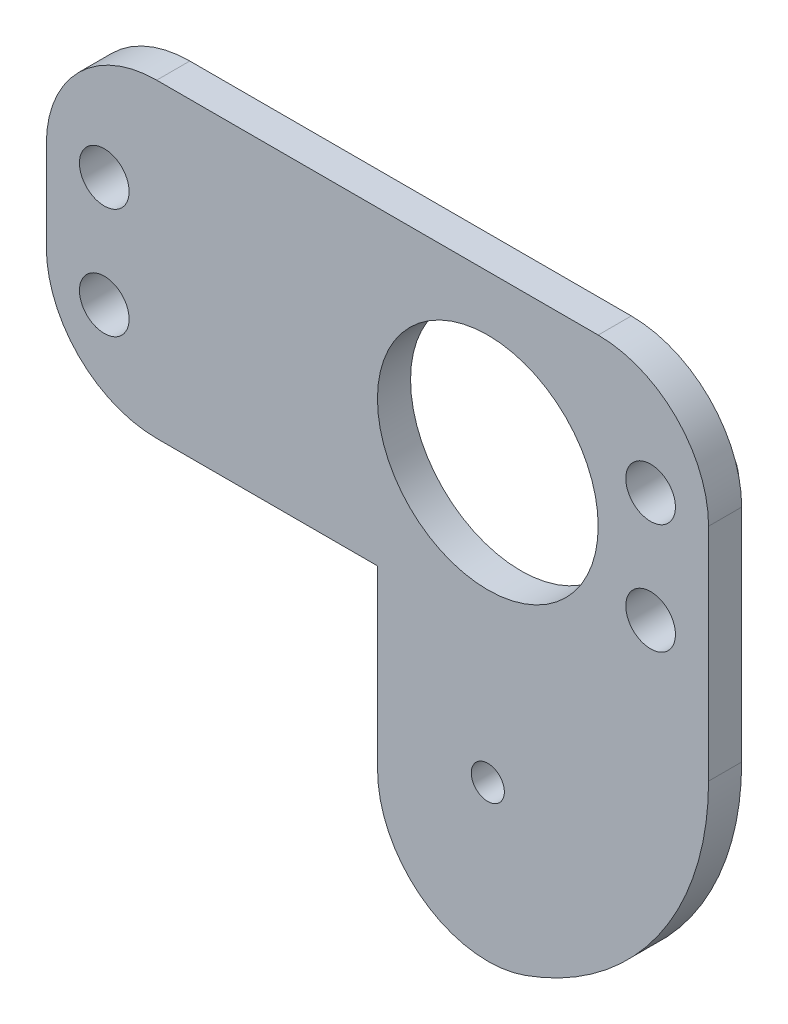
SolidWorks part; units mm, degrees
ref_plane "前视基准面" through (0, 0, 0) normal (0, 0, 1) x (1, 0, 0)
ref_plane "上视基准面" through (0, 0, 0) normal (0, 1, 0) x (1, 0, 0)
ref_plane "右视基准面" through (0, 0, 0) normal (1, 0, 0) x (0, 0, -1)
sketch "草图3" plane through (0, 0, 0) normal (0, 0, 1) x (1, 0, 0)
  line L0 (60.2665, 6.5325) -> (60.2665, 16.5325)
  line L1 (10.7665, 16.5325) -> (10.7665, 6.5325)
  line L2 (10.7665, 16.5325) -> (60.2665, 16.5325)
  circle A0 centre (60.2665, 16.5325) radius 3
  circle A1 centre (60.2665, 6.5325) radius 3
  circle A6 centre (10.7665, 6.5325) radius 3
  circle A7 centre (10.7665, 16.5325) radius 3
  dimension "D1" = 6
  dimension "D2" = 6
  dimension "D4" = 6
  dimension "D5" = 6
  dimension "D3" = 10
  dimension "D6" = 49.5
  dimension "D7" = 49.5
  dimension "D8" = 10
extrude "凸台-拉伸6" add sketch "草图3" along normal blind 2 contours A6 | A0 | A1 | A7
sketch "草图11" plane through (0, 0, 2) normal (0, 0, 1) x (1, 0, 0)
  circle A0 centre (10.7665, 16.5325) radius 2.25
  circle A1 centre (10.7665, 6.5325) radius 2.25
  circle A2 centre (60.2665, 16.5325) radius 2.25
  circle A3 centre (60.2665, 6.5325) radius 2.25
  dimension "D1" = 4.5
  dimension "D2" = 4.5
  dimension "D3" = 4.5
  dimension "D4" = 4.5
extrude "切除-拉伸2" cut sketch "草图11" against normal blind 2 and the other way blind 10
sketch "草图12" plane through (0, 0, 2) normal (0, 0, 1) x (1, 0, 0)
  line L4 (10.7665, 16.5325) -> (60.2665, 6.5325) construction
  line L5 (10.7665, 6.5325) -> (60.2665, 16.5325) construction
  line L6 (60.2665, 16.5325) -> (60.2665, 6.5325) construction
  line L7 (5.5165, 26.5325) -> (65.5165, 26.5325)
  line L8 (5.5165, 26.5325) -> (5.5165, -28.4675)
  line L9 (5.5165, -28.4675) -> (65.5165, -28.4675)
  line L10 (65.5165, 26.5325) -> (65.5165, -28.4675)
  circle A4 centre (45.5165, 11.5325) radius 10
  point P8 (35.5165, 11.5325)
  point P9 (35.5165, 26.5325)
  point P10 (-46.6091, 14.6442)
  point P11 (60.2665, 11.5325)
  dimension "D5" = 20
  dimension "D1" = 60
  dimension "D2" = 55
  dimension "D3" = 15
  dimension "D4" = 14.75
extrude "凸台-拉伸7" add sketch "草图12" along normal blind 3 contours L7 L10 L9 L8
sketch "草图14" plane through (0, 0, 2) normal (0, 0, -1) x (-1, 0, 0)
  line L0 (-60.2665, 16.5325) -> (-60.2665, 6.5325) construction
  circle A0 centre (-60.2665, 6.5325) radius 2.25 construction
  circle A1 centre (-60.2665, 6.5325) radius 2.25
  circle A2 centre (-60.2665, 16.5325) radius 2.25 construction
  circle A3 centre (-60.2665, 16.5325) radius 2.25
  circle A4 centre (-10.7665, 6.5325) radius 2.25 construction
  circle A5 centre (-10.7665, 16.5325) radius 2.25 construction
  circle A6 centre (-10.7665, 6.5325) radius 2.25
  circle A7 centre (-10.7665, 16.5325) radius 2.25
  circle A8 centre (-45.5165, 11.5325) radius 10
  point P14 (-60.2665, 11.5325)
  point P15 (0.1696, -0.033)
  dimension "D2" = 20
  dimension "D1" = 14.75
extrude "切除-拉伸3" cut sketch "草图14" against normal blind 3
sketch "草图15" plane through (0, 0, 2) normal (0, 0, -1) x (-1, 0, 0)
  circle A0 centre (-45.5165, 11.5325) radius 10 construction
  circle A1 centre (-45.5165, 11.5325) radius 10
  circle A2 centre (-45.5165, -13.5675) radius 1.5
  dimension "D2" = 3
  dimension "D1" = 25.1
extrude "切除-拉伸4" cut sketch "草图15" against normal blind 3
fillet "圆角3" radius 25 1 edges at (65.5165, -28.4675, 3.5)
fillet "圆角4" radius 10 2 edges at (65.5165, 26.5325, 3.5) (5.5165, 26.5325, 3.5)
sketch "草图16" plane through (0, 0, 5) normal (0, 0, 1) x (1, 0, 0)
  line L0 (5.5165, -1.5783) -> (35.5306, -1.5783)
  line L1 (5.5165, 16.5325) -> (5.5165, -28.4675) construction
  line L2 (35.5306, -1.5783) -> (35.5306, -28.4675)
  line L3 (5.5165, -28.4675) -> (40.5165, -28.4675) construction
  line L4 (5.5165, -28.4675) -> (35.5306, -28.4675)
  line L5 (5.5165, -1.5783) -> (5.5165, -28.4675)
  line L6 (5.5165, 16.5325) -> (5.5165, -1.5783) construction
  line L7 (35.5306, -28.4675) -> (40.5165, -28.4675) construction
extrude "切除-拉伸5" cut sketch "草图16" against normal blind 10
fillet "圆角6" radius 10 2 edges at (5.5165, -1.5783, 3.5) (35.5306, -28.4675, 3.5)
